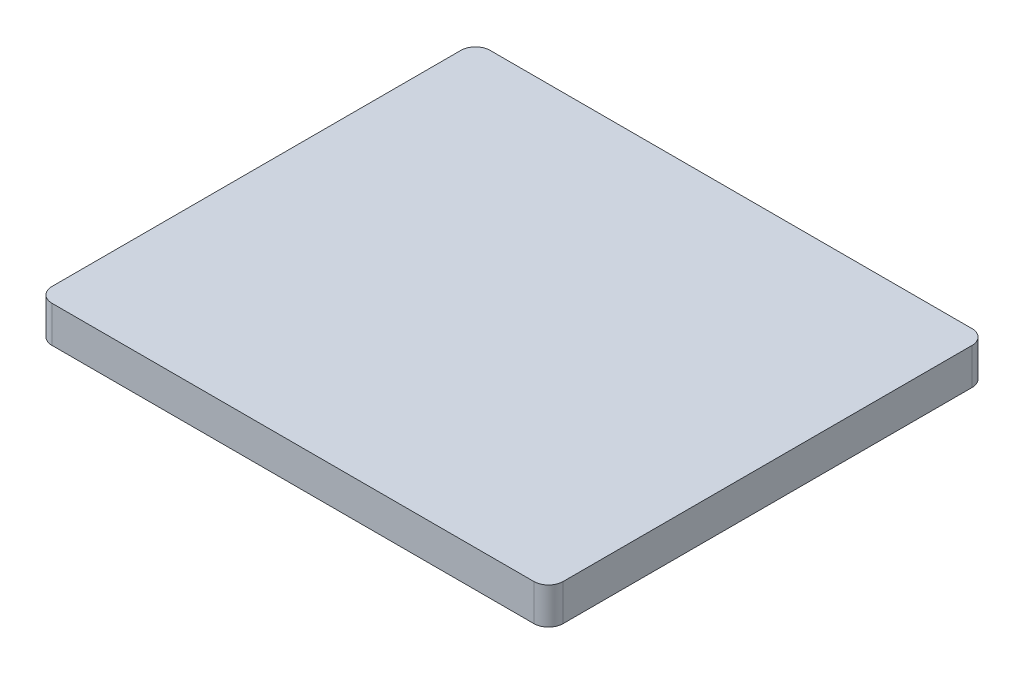
SolidWorks part; units mm, degrees
ref_plane "Front Plane" through (0, 0, 0) normal (0, 0, 1) x (1, 0, 0)
ref_plane "Top Plane" through (0, 0, 0) normal (0, 1, 0) x (1, 0, 0)
ref_plane "Right Plane" through (0, 0, 0) normal (1, 0, 0) x (0, 0, -1)
sketch "Sketch1" plane through (0, 0, 0) normal (0, 1, 0) x (1, 0, 0)
  line L1 (-35, 30) -> (35, 30)
  line L2 (-35, 30) -> (-35, -30)
  line L3 (-35, -30) -> (35, -30)
  line L4 (35, 30) -> (35, -30)
extrude "Boss-Extrude2" add sketch "Sketch1" along normal blind 5 contours L4 L1 L2 L3 region at (0, 0, 0)
sketch "Sketch15" plane through (0, 0, 0) normal (0, 1, 0) x (-1, 0, 0)
  line L1 (-14.5, -4.5) -> (14.5, -4.5)
  line L2 (-14.5, -4.5) -> (-14.5, 4.5)
  line L3 (-14.5, 4.5) -> (14.5, 4.5)
  line L4 (14.5, -4.5) -> (14.5, 4.5)
  line L5 (-14.5, -4.5) -> (14.5, 4.5) construction
  line L6 (-14.5, 4.5) -> (14.5, -4.5) construction
  point P0 (0, 0)
extrude "Boss-Extrude13" add sketch "Sketch15" against normal blind 20
sketch "Sketch16" plane through (0, 0, 4.5) normal (0, 0, 1) x (1, 0, 0)
  circle A0 centre (0, -12) radius 5.5
extrude "Cut-Extrude3" cut sketch "Sketch16" against normal through all
fillet "Fillet1" radius 2 16 edges at (0, 0, -4.5) (14.5, 0, 0) (-14.5, 0, 0) (-35, 2.5, 30) (35, 2.5, 30) (-35, 2.5, -30) (35, 2.5, -30) (0, -20, 4.5) (0, -20, -4.5) (14.5, -10, 4.5) (0, 0, 4.5) (14.5, -10, -4.5) (14.5, -20, 0) (-14.5, -20, 0) (-14.5, -10, -4.5) (-14.5, -10, 4.5)
sketch "Sketch17" plane through (0, 0, 4.5) normal (0, 0, 1) x (1, 0, 0)
  point P1 (0, -12)
sketch "Sketch18" plane through (0, 0, -4.5) normal (0, 0, -1) x (-1, 0, 0)
  point P1 (0, -12)
